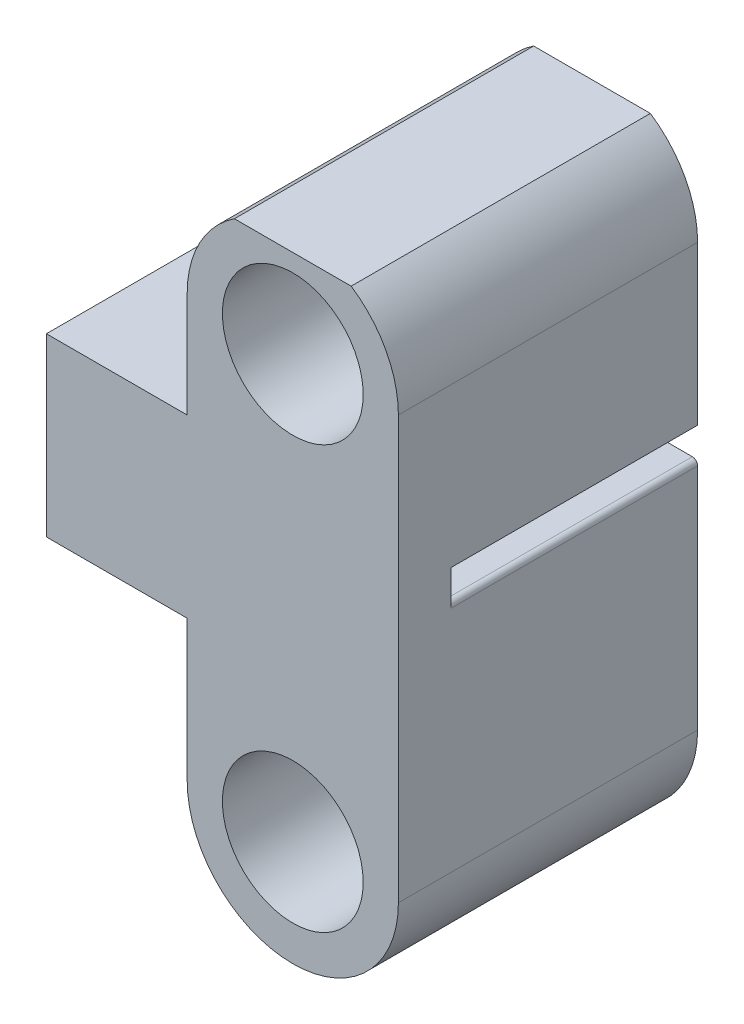
SolidWorks part; units mm, degrees
ref_plane "Front Plane" through (0, 0, 0) normal (0, 0, 1) x (1, 0, 0)
ref_plane "Top Plane" through (0, 0, 0) normal (0, 1, 0) x (1, 0, 0)
ref_plane "Right Plane" through (0, 0, 0) normal (1, 0, 0) x (0, 0, -1)
sketch "Sketch1" plane through (0, 0, 0) normal (0, 0, 1) x (1, 0, 0)
  line L0 (0, 0) -> (0, -12) construction
  line L1 (-3, 0) -> (-3, -12)
  line L2 (3, 0) -> (3, -12)
  arc A0 (3, 0) -> (-3, 0) centre (0, 0) ccw
  arc A1 (-3, -12) -> (3, -12) centre (0, -12) ccw
  circle A2 centre (0, 0) radius 2
  circle A3 centre (0, -12) radius 2
  dimension "D2" = 6
  dimension "D6" = 4
  dimension "D7" = 4
  dimension "D1" = 12
extrude "Boss-Extrude1" add sketch "Sketch1" along normal blind 8.5
sketch "Sketch2" plane through (3, 0, 0) normal (1, 0, 0) x (0, 0, -1)
  line L0 (-8.5, -6) -> (0, -6) construction
  line L1 (-8.5, -12) -> (-8.5, 0) construction
  line L2 (0, -12) -> (0, 0) construction
  line L3 (-4.25, 0) -> (-4.25, -12) construction
  line L4 (-8.5, 0) -> (0, 0) construction
  line L5 (-8.5, -12) -> (0, -12) construction
  circle A0 centre (-4.25, -8.5) radius 2
  dimension "D1" = 4
  dimension "D2" = 2.5
extrude "Cut-Extrude1" [suppressed] cut sketch "Sketch2" against normal through all
sketch "Sketch3" [suppressed] plane through (3, 0, 0) normal (1, 0, 0) x (0, 0, -1)
  line L1 (-0.6416, -8.5) -> (-2.4458, -5.375)
  line L2 (-2.4458, -5.375) -> (-6.0542, -5.375)
  line L3 (-6.0542, -5.375) -> (-7.8584, -8.5)
  line L4 (-7.8584, -8.5) -> (-6.0542, -11.625)
  line L5 (-6.0542, -11.625) -> (-2.4458, -11.625)
  line L6 (-2.4458, -11.625) -> (-0.6416, -8.5)
  line L7 (-1.8684, -4.375) -> (-6.6316, -4.375)
  line L8 (-6.6316, -4.375) -> (-9.0131, -8.5)
  line L9 (-9.0131, -8.5) -> (-6.6316, -12.625)
  line L10 (-6.6316, -12.625) -> (-1.8684, -12.625)
  line L11 (-1.8684, -12.625) -> (0.5131, -8.5)
  line L12 (0.5131, -8.5) -> (-1.8684, -4.375)
  circle A0 centre (-4.25, -8.5) radius 3.125 construction
  circle A1 centre (-4.25, -8.5) radius 4.125 construction
  dimension "D1" = 6.25
  dimension "D2" = 1
extrude "Boss-Extrude2" [suppressed] add sketch "Sketch3" along normal blind 2 and the other way blind 0.5
sketch "Sketch4" [suppressed] plane through (-3, 0, 0) normal (-1, 0, 0) x (0, 0, 1)
  line L0 (4.25, 0) -> (4.25, -6.5) construction
  line L1 (8.5, 0) -> (0, 0) construction
  line L3 (0.75, -2.75) -> (7.75, -2.75)
  line L4 (0.75, -2.75) -> (0.75, -5.75)
  line L5 (0.75, -5.75) -> (7.75, -5.75)
  line L6 (7.75, -2.75) -> (7.75, -5.75)
  line L7 (0.75, -2.75) -> (7.75, -5.75) construction
  line L8 (0.75, -5.75) -> (7.75, -2.75) construction
  circle A0 centre (4.25, -8.5) radius 2 construction
  point P7 (4.25, -4.25)
  dimension "D1" = 7
  dimension "D2" = 3
  dimension "D3" = 2.75
extrude "Cut-Extrude2" [suppressed] cut sketch "Sketch4" against normal through all
sketch "Sketch5" plane through (-3, 0, 0) normal (-1, 0, 0) x (0, 0, 1)
  line L0 (4.25, 0) -> (4.25, -12) construction
  line L1 (8.5, 0) -> (0, 0) construction
  line L2 (8.5, -12) -> (0, -12) construction
  line L3 (0, -6) -> (8.5, -6) construction
  line L4 (0, 0) -> (0, -12) construction
  line L5 (8.5, 0) -> (8.5, -12) construction
  line L7 (0, -15) -> (8.5, -15)
  line L8 (0, -15) -> (0, 3)
  line L9 (0, 3) -> (8.5, 3)
  line L10 (8.5, -15) -> (8.5, 3)
  line L11 (0, -15) -> (8.5, 3) construction
  line L12 (0, 3) -> (8.5, -15) construction
  point P12 (4.25, -6)
extrude "Cut-Extrude3" [suppressed] cut sketch "Sketch5" against normal through all flip side to cut
sketch "Sketch9" plane through (-3, 0, 0) normal (-1, 0, 0) x (0, 0, 1)
  line L0 (8.5, 0) -> (8.5, -12) construction
  line L1 (0, -3) -> (8.5, -3)
  line L2 (0, -3) -> (0, -8)
  line L3 (0, -8) -> (8.5, -8)
  line L4 (8.5, -3) -> (8.5, -8)
  line L5 (0, 0) -> (0, -12) construction
  line L6 (8.5, 0) -> (0, 0) construction
  dimension "D1" = 5
  dimension "D2" = 3
extrude "Boss-Extrude4" add sketch "Sketch9" along normal blind 4
sketch "Sketch6" plane through (3, 0, 0) normal (1, 0, 0) x (0, 0, -1)
  line L0 (0, -12) -> (0, 0) construction
  line L1 (0, -4.5) -> (-7, -4.5)
  line L2 (0, -4.5) -> (0, -6.1)
  line L3 (0, -6.1) -> (-7, -6.1)
  line L4 (-7, -4.5) -> (-7, -6.1)
  dimension "D1" = 1.6
  dimension "D2" = 4.5
  dimension "D3" = 7
extrude "Cut-Extrude5" cut sketch "Sketch6" against normal through all
sketch "Sketch7" plane through (0, 0, 7) normal (0, 0, -1) x (-1, 0, 0)
  line L0 (-3, -6.1) -> (-3, -5.5)
  line L1 (-3, -4.5) -> (-3, -6.1) construction
  line L2 (-2.85, -5.35) -> (-2.15, -5.35)
  line L3 (-2, -5.5) -> (-2, -6.1)
  line L4 (7, -6.1) -> (-3, -6.1) construction
  line L5 (-2, -6.1) -> (-3, -6.1)
  line L6 (-0.85, -5.35) -> (-0.15, -5.35)
  line L7 (0, -5.5) -> (0, -6.1)
  line L8 (0, -6.1) -> (-1, -6.1)
  line L9 (-1, -6.1) -> (-1, -5.5)
  line L10 (1.15, -5.35) -> (1.85, -5.35)
  line L11 (2, -5.5) -> (2, -6.1)
  line L12 (2, -6.1) -> (1, -6.1)
  line L13 (1, -6.1) -> (1, -5.5)
  line L14 (3.15, -5.35) -> (3.85, -5.35)
  line L15 (4, -5.5) -> (4, -6.1)
  line L16 (4, -6.1) -> (3, -6.1)
  line L17 (3, -6.1) -> (3, -5.5)
  line L18 (5.15, -5.35) -> (5.85, -5.35)
  line L19 (6, -5.5) -> (6, -6.1)
  line L20 (6, -6.1) -> (5, -6.1)
  line L21 (5, -6.1) -> (5, -5.5)
  arc A0 (-2.15, -5.35) -> (-2, -5.5) centre (-2.15, -5.5) cw
  arc A1 (-3, -5.5) -> (-2.85, -5.35) centre (-2.85, -5.5) cw
  arc A2 (-1, -5.5) -> (-0.85, -5.35) centre (-0.85, -5.5) cw
  arc A3 (-0.15, -5.35) -> (0, -5.5) centre (-0.15, -5.5) cw
  arc A4 (1, -5.5) -> (1.15, -5.35) centre (1.15, -5.5) cw
  arc A5 (1.85, -5.35) -> (2, -5.5) centre (1.85, -5.5) cw
  arc A6 (3, -5.5) -> (3.15, -5.35) centre (3.15, -5.5) cw
  arc A7 (3.85, -5.35) -> (4, -5.5) centre (3.85, -5.5) cw
  arc A8 (5, -5.5) -> (5.15, -5.35) centre (5.15, -5.5) cw
  arc A9 (5.85, -5.35) -> (6, -5.5) centre (5.85, -5.5) cw
  point P11 (-2, -5.35)
  point P14 (-3, -5.35)
  dimension "D3" = 0.15
  dimension "D1" = 1
  dimension "D2" = 0.75
  dimension "D4" = 5
extrude "Boss-Extrude3" add sketch "Sketch7" along normal through all
sketch "Sketch10" plane through (0, 0, 8.5) normal (0, 0, 1) x (1, 0, 0)
  line L1 (-2.5, 3.5) -> (2.5, 3.5)
  line L2 (-2.5, 3.5) -> (-2.5, 2.5)
  line L3 (-2.5, 2.5) -> (2.5, 2.5)
  line L4 (2.5, 3.5) -> (2.5, 2.5)
  line L5 (-2.5, 3.5) -> (2.5, 2.5) construction
  line L6 (-2.5, 2.5) -> (2.5, 3.5) construction
  arc A0 (3, 0) -> (-3, 0) centre (0, 0) ccw construction
  point P0 (0, 3)
  dimension "D1" = 1
  dimension "D2" = 5
extrude "Cut-Extrude6" cut sketch "Sketch10" against normal through all
equation "\"X-ROD-SPACING\"=45"
equation "\"Y-ROD-SPACING\"=75"
equation "\"Z-ROD-SPACING\"=17.5"
equation "\"Y-BED-OFFSET\"=2"
equation "\"Y-BED-ROD-INSET\"=3.5"
equation "\"Y-BED-SCREW-SPACING\"=209"
equation "\"Y-BED-SCREW-CUTOUT-SLOT-HEIGHT\"=2"
equation "\"T-SLOT-NUT-FILLET-RADIUS\"=0.5"
equation "\"T-SLOT-SCREW-SHAFT-RADIUS\"=1.55"
equation "\"T-SLOT-SCREW-SHAFT-CUTOUT-LENGTH\"=11.0"
equation "\"T-SLOT-NUT-DEPTH\"=3.5"
equation "\"T-SLOT-NUT-WIDTH\"=2.85"
equation "\"T-SLOT-NUT-END-DISTANCE\"=8"
equation "\"ACRYLIC-THICKNESS\"=10"
equation "\"ACRYLIC-THICKNESS2\"=4.5"
equation "\"ACRYLIC-TAB-CUTOUT-SIZE\"=\"ACRYLIC-THICKNESS\"+\"ACRYLIC-TAB-TOLERANCE\"*2"
equation "\"ACRYLIC-TAB-TOLERANCE\"=-.05"
equation "\"ACRYLIC-TAB-WIDTH\"=\"ACRYLIC-THICKNESS\""
equation "\"ACRYLIC-M3-HOLE\"=2.9"
equation "\"SMOOTHROD-CAP-SCREW-DISTANCE\"=20"
equation "\"FRAME-WIDTH-INNER\"=370"
equation "\"NEMA17-HOLE-SPACING\"=31"
equation "\"NEMA17-CENTRAL-CUTOUT\"=22.5"
equation "\"Z-BRACKET-REACH\"=55"
equation "\"Z-ROD-INSET\"=16"
equation "\"TOP-BRACKET-SPACING\"=40"
equation "\"SMOOTHROD-X-LENGTH\"=350"
equation "\"SMOOTHROD-Y-LENGTH\"=350"
equation "\"SMOOTHROD-Z-LENGTH\"=350"
equation "\"SMOOTHROD-TIGHTENING-HEADROOM\"=.25"
equation "\"LEADSCREW-Z-LENGTH\"=300"
equation "\"SCREW-LENGTH-FRAME\"=\"ACRYLIC-THICKNESS\" + 10"
equation "\"SCREW-LENGTH-MOTOR\"=\"ACRYLIC-THICKNESS\" + 5"
equation "\"SCREW-LENGTH-EXTRUDER\"=28"
equation "\"SCREW-HEAD-RADIUS\"=6"
equation "\"PRINTED-M3-HOLE\"=3.5"
equation "\"PRINTED-X-SMOOTHROD-DIAMETER\"=8.4"
equation "\"PRINTED-X-SMOOTHROD-CUTOUT\"=10"
equation "\"PRINTED-X-BASE-HEIGHT\"=10"
equation "\"PRINTED-LM8UU-CUTOUT-SIZE\"=15.5"
equation "\"PRINTED-LM8UU-CUTOUT-LENGTH\"=24.5"
equation "\"PRINTED-X-IDLER-HEIGHT\"=16"
equation "\"PRINTED-M3-NUT-AF\"=6.25"
equation "\"PSU-MOUNTING-WIDTH\"=95"
equation "\"PSU-MOUNTING-HEIGHT\"=177"
equation "\"Y-BELT-TO-ROD-DISTANCE\"=20"
equation "\"SPOOL-HOLDER-ROD-SPACING\"=150"
equation "\"ACRYLIC-X-CARRIAGE-WIDTH\"=55"
equation "\"ACRYLIC-X-CARRIAGE-HEIGHT\"=75"
equation "\"ACRYLIC-X-CARRIAGE-LM8UU-CUTOUT-WIDTH\"=24.25"
equation "\"ACRYLIC-X-CARRIAGE-LM8UU-CUTOUT-HEIGHT\"=11.0"
equation "\"ACRYLIC-X-CARRIAGE-SCREW-SPACING-X\"=15"
equation "\"ACRYLIC-X-CARRIAGE-SCREW-SPACING-Y\"=33"
equation "\"ACRYLIC-X-CARRIAGE-CENTER-TAB-SPACING\"=14"
equation "\"ACRYLIC-X-CARRIAGE-EXTRUDER-OFFSET\"=26"
equation "\"ACRYLIC-X-CARRIAGE-EXTRUDER-ANGLE\"=90"
equation "\"ACRYLIC-X-CARRIAGE-EXTRUDER-SHELF-DEPTH\"=\"ACRYLIC-X-CARRIAGE-EXTRUDER-OFFSET\" + 28"
equation "\"ACRYLIC-X-CARRIAGE-EXTRUDER-BRACE-SPACING\"=23"
equation "\"ACRYLIC-X-CARRIAGE-EXTRUDER-BRACE-TAB-OFFSET\"=20"
equation "\"ACRYLIC-X-CARRIAGE-EXTRUDER-BRACE-HEIGHT\"=35"
equation "\"ACRYLIC-X-CARRIAGE-EXTRUDER-BRACE-SCREW-SPACING\"=22"
equation "\"ACRYLIC-X-CARRIAGE-DUAL-WIDTH-MULTIPLIER\"=1.65"
equation "\"ACRYLIC-X-CARRIAGE-DUAL-HOTEND-SPACING\"=42"
equation "\"ACRYLIC-X-CARRIAGE-DUAL-WIDTH\"=75"
equation "\"ACRYLIC-X-CARRIAGE-DUAL-HOTEND-SEPARATION\"=36"
equation "\"ACRYLIC-X-CARRIAGE-DUAL-MOUNT-PLATE-DEPTH\"=75"
equation "\"ACRYLIC-X-CARRIAGE-DUAL-MOUNT-BRACE-WIDTH\"=33"
equation "\"ACRYLIC-X-CARRIAGE-DUAL-MOUNT-SCREW-WIDTH\"=40"
equation "\"BLOWER-FAN-WIDTH\"=15"
equation "\"D1@Sketch3\"=\"PRINTED-M3-NUT-AF\""
